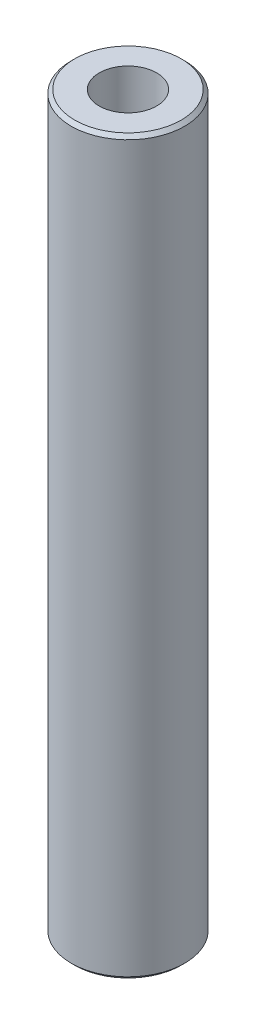
SolidWorks part; units mm, degrees
ref_plane "Front Plane" through (0, 0, 0) normal (0, 0, 1) x (1, 0, 0)
ref_plane "Top Plane" through (0, 0, 0) normal (0, 1, 0) x (1, 0, 0)
ref_plane "Right Plane" through (0, 0, 0) normal (1, 0, 0) x (0, 0, -1)
sketch "Sketch1" plane through (0, 0, 0) normal (0, 1, 0) x (1, 0, 0)
  circle A0 centre (0, 0) radius 32.5
  dimension "SHAFT_OD" = 65
extrude "Boss-Extrude1" add sketch "Sketch1" along normal blind 419.3541
sketch "Sketch2" plane through (0, 0, 0) normal (0, 1, 0) x (1, 0, 0)
  circle A0 centre (0, 0) radius 16.4763
  dimension "BORE_D" = 32.9526
extrude "Cut-Extrude1" cut sketch "Sketch2" along normal through all
chamfer "Chamfer1" distance 2.0164 angle 45 2 edges at (0, 419.3541, 32.5) (0, 0, 32.5)
